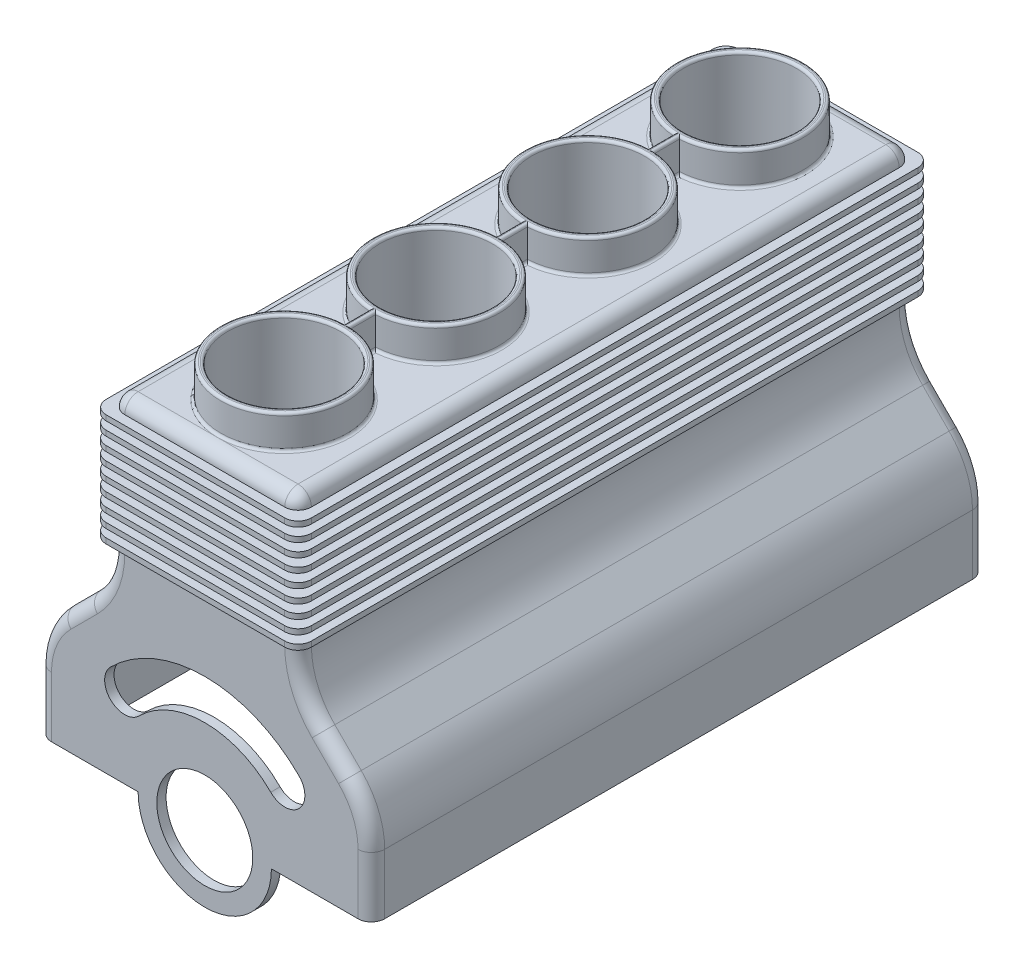
SolidWorks part; units mm, degrees
material "Gray Cast Iron (SN)"
ref_plane "Front Plane" through (0, 0, 0) normal (0, 0, 1) x (1, 0, 0)
ref_plane "Top Plane" through (0, 0, 0) normal (0, 1, 0) x (1, 0, 0)
ref_plane "Right Plane" through (0, 0, 0) normal (1, 0, 0) x (0, 0, -1)
sketch "Sketch1" plane through (0, 0, 0) normal (0, 0, 1) x (1, 0, 0)
  line L0 (0, 0) -> (84554.6019, 0) construction
  line L1 (0, 0) -> (0, 84554.6019) construction
  line L2 (-60, 250) -> (60, 250)
  line L3 (70, 240) -> (70, 149.8528)
  line L4 (125, 45.1472) -> (125, 0)
  line L5 (125, 0) -> (36, 0)
  line L6 (107.4264, 87.5736) -> (87.5736, 107.4264)
  line L7 (-125, 0) -> (-36, 0)
  line L8 (-125, 45.1472) -> (-125, 0)
  line L39 (-70, 240) -> (-70, 149.8528)
  line L40 (-107.4264, 87.5736) -> (-87.5736, 107.4264)
  arc A0 (70, 149.8528) -> (87.5736, 107.4264) centre (130, 149.8528) ccw
  arc A1 (107.4264, 87.5736) -> (125, 45.1472) centre (65, 45.1472) cw
  arc A2 (36, 0) -> (-36, 0) centre (0, 0) ccw
  arc A3 (-107.4264, 87.5736) -> (-125, 45.1472) centre (-65, 45.1472) ccw
  arc A5 (60, 250) -> (70, 240) centre (60, 240) cw
  arc A6 (-70, 240) -> (-60, 250) centre (-60, 240) cw
  arc A7 (-70, 149.8528) -> (-87.5736, 107.4264) centre (-130, 149.8528) cw
  arc A8 (-36, 0) -> (36, 0) centre (0, 0) ccw
  arc A9 (-50, 0) -> (50, 0) centre (0, 0) ccw
  point P16 (120.4328, 68.1082)
  point P25 (70, 125)
  point P29 (0, 250)
  point P32 (70, 250)
  point P35 (-70, 250)
  point P36 (-70, 125)
  dimension "D1" = 36
  dimension "D8" = 10
  dimension "D9" = 60
  dimension "D10" = 50
  dimension "D2" = 140
  dimension "D3" = 250
  dimension "D4" = 250
  dimension "D5" = 60
  dimension "D6" = 135
  dimension "D7" = 125
extrude "Boss-Extrude1" add sketch "Sketch1" along normal mid plane 461 contours A6 A3 L8 L7 A2 L5 L4 A1 L6 A0 | L7 A9 L5 A8 region at (0, 111.7838, 0) region at (-43, -1.118, 0)
sketch "Sketch2" plane through (0, 250, 0) normal (0, 1, 0) x (1, 0, 0)
  line L0 (-50000, 0) -> (50000, 0) construction
  line L1 (-2, 9.5421) -> (-2, -9.5421)
  line L2 (-2, 123.5421) -> (-2, 104.4579)
  line L3 (2, 123.5421) -> (2, 104.4579)
  line L4 (0, 50000) -> (0, -50000) construction
  line L5 (2, 9.5421) -> (2, -9.5421)
  line L6 (-2, -104.4579) -> (-2, -123.5421)
  line L7 (2, -104.4579) -> (2, -123.5421)
  circle A0 centre (0, -171) radius 42.5
  circle A1 centre (0, -57) radius 42.5
  circle A2 centre (0, 57) radius 42.5
  circle A3 centre (0, 171) radius 42.5
  arc A4 (-2, -123.5421) -> (2, -123.5421) centre (0, -171) ccw
  arc A5 (-2, -9.5421) -> (-2, -104.4579) centre (0, -57) ccw
  arc A6 (-2, 104.4579) -> (-2, 9.5421) centre (0, 57) ccw
  arc A7 (2, 123.5421) -> (-2, 123.5421) centre (0, 171) ccw
  arc A8 (2, 9.5421) -> (2, 104.4579) centre (0, 57) ccw
  arc A9 (2, -104.4579) -> (2, -9.5421) centre (0, -57) ccw
  point P21 (0, 0)
  dimension "D1" = 85
  dimension "D4" = 95
  dimension "D3" = 114
  dimension "D6" = 4
  dimension "D2" = 4
  dimension "D5" = 4
ref_plane "Plane1" through (0, 240, 0) normal (0, 1, 0) x (1, 0, 0)
sketch "Sketch3" plane through (0, 240, 0) normal (0, 1, 0) x (1, 0, 0)
  line L0 (70, -230.5) -> (70, 230.5) construction
  line L1 (-67, 237.5) -> (67, 237.5)
  line L2 (-77, 227.5) -> (-77, -227.5)
  line L3 (-67, -237.5) -> (67, -237.5)
  line L4 (77, 227.5) -> (77, -227.5)
  line L5 (-77, 237.5) -> (77, -237.5) construction
  line L6 (-77, -237.5) -> (77, 237.5) construction
  line L10 (60, 230.5) -> (-60, 230.5)
  line L11 (-60, 230.5) -> (-60, -230.5)
  line L12 (-60, -230.5) -> (60, -230.5)
  line L13 (60, -230.5) -> (60, 230.5)
  line L14 (60, 230.5) -> (-60, 230.5)
  line L15 (-60, 230.5) -> (-60, -230.5)
  line L16 (-60, -230.5) -> (60, -230.5)
  line L17 (60, -230.5) -> (60, 230.5)
  arc A0 (-67, 237.5) -> (-77, 227.5) centre (-67, 227.5) ccw
  arc A1 (67, 237.5) -> (77, 227.5) centre (67, 227.5) cw
  arc A2 (67, -237.5) -> (77, -227.5) centre (67, -227.5) ccw
  arc A3 (-77, -227.5) -> (-67, -237.5) centre (-67, -227.5) ccw
  point P0 (0, 0)
  dimension "D4" = 10
  dimension "D2" = 7
  dimension "D3" = 7
  dimension "D1" = 0
extrude "Boss-Extrude2" add sketch "Sketch3" against normal blind 4
pattern_linear "LPattern1" count 9 spacing 10 along (0, -1, 0) of "Boss-Extrude2"
extrude "Cut-Extrude1" cut sketch "Sketch2" against normal blind 114 contours A3 | A2 | A0 | A1 region at (0, 250, 171) region at (0, 250, 57) region at (0, 250, -57) region at (0, 250, -171)
fillet "Fillet2" radius 10 58 edges at (-67.0711, 247.0711, -230.5) (67.0711, 247.0711, -230.5) (-125, 22.5736, -230.5) (-120.4328, 68.1082, -230.5) (-67.0711, 247.0711, 230.5) (67.0711, 247.0711, 230.5) (70, 152.9264, -230.5) (74.5672, 126.8918, -230.5) (97.5, 97.5, -230.5) (125, 22.5736, -230.5) (70, 152.9264, 230.5) (125, 22.5736, 230.5) (120.4328, 68.1082, 230.5) (97.5, 97.5, 230.5) (-70, 152.9264, 230.5) (-74.5672, 126.8918, 230.5) (-97.5, 97.5, 230.5) (-125, 22.5736, 230.5) (0, 250, -230.5) (70, 233, -230.5) (70, 223, -230.5) (70, 213, -230.5) (70, 203, -230.5) (70, 193, -230.5) (70, 183, -230.5) (70, 173, -230.5) (70, 163, -230.5) (-70, 193, -230.5) (-70, 203, -230.5) (-70, 213, -230.5) (-70, 223, -230.5) (-70, 233, -230.5) (-70, 183, -230.5) (-70, 173, -230.5) (-70, 163, -230.5) (-97.5, 97.5, -230.5) (-70, 152.9264, -230.5) (-74.5672, 126.8918, -230.5) (-70, 163, 230.5) (-70, 173, 230.5) (-70, 183, 230.5) (-70, 193, 230.5) (-70, 203, 230.5) (-70, 213, 230.5) (-70, 223, 230.5) (-70, 233, 230.5) (0, 250, 230.5) (70, 233, 230.5) (70, 223, 230.5) (70, 213, 230.5) (70, 203, 230.5) (70, 193, 230.5) (70, 183, 230.5) (70, 173, 230.5) (70, 163, 230.5) (120.4328, 68.1082, -230.5) (74.5672, 126.8918, 230.5) (-120.4328, 68.1082, 230.5)
extrude "Boss-Extrude3" add sketch "Sketch2<3>" along normal blind 25
sketch "Sketch2<3>" plane through (0, 250, 0) normal (0, 1, 0) x (1, 0, 0) same geometry as "Sketch2"
fillet "Fillet3" radius 2 12 edges at (-2, 275, 114) (-47.5, 275, 57) (-2, 275, 0) (-47.5, 275, -57) (-2, 275, -114) (0, 275, -218.5) (2, 275, -114) (2, 275, 0) (47.5, 275, 57) (2, 275, 114) (0, 275, 218.5) (47.5, 275, -57)
fillet "Fillet4" radius 2 16 edges at (-42.5, 275, -57) (-42.5, 275, 57) (-42.5, 275, 171) (0, 250, 218.5) (2, 250, 114) (47.5, 250, 57) (2, 250, 0) (47.5, 250, -57) (2, 250, -114) (0, 250, -218.5) (-2, 250, -114) (-47.5, 250, -57) (-2, 250, 0) (-47.5, 250, 57) (-2, 250, 114) (-42.5, 275, -171)
sketch "Sketch4" plane through (0, 0, 0) normal (0, 0, 1) x (1, 0, 0)
  line L0 (55, 149.8528) -> (55, 151)
  line L1 (55, 151) -> (-55, 151)
  line L2 (-55, 151) -> (-55, 149.8528)
  line L3 (-76.967, 96.8198) -> (-96.8198, 76.967)
  line L4 (-110, 45.1472) -> (-110, 0)
  line L7 (110, 0) -> (110, 45.1472)
  line L8 (96.8198, 76.967) -> (76.967, 96.8198)
  line L10 (-110, 45.1472) -> (-110, 5) construction
  line L11 (110, 5) -> (110, 45.1472) construction
  line L13 (50, 0) -> (115, 0) construction
  line L18 (60, 149.8528) -> (60, 156)
  line L19 (60, 156) -> (-60, 156)
  line L20 (-60, 156) -> (-60, 149.8528)
  line L21 (-80.5025, 100.3553) -> (-100.3553, 80.5025)
  line L22 (-115, 45.1472) -> (-115, 0)
  line L23 (-115, 0) -> (-50, 0)
  line L24 (50, 0) -> (115, 0)
  line L25 (115, 0) -> (115, 45.1472)
  line L26 (100.3553, 80.5025) -> (80.5025, 100.3553)
  line L32 (-115, 0) -> (-50, 0)
  line L33 (50, 0) -> (110, 0)
  line L34 (115, 0) -> (115, 45.1472) construction
  line L36 (-110, 5) -> (-54.7723, 5) construction
  line L37 (54.7723, 5) -> (110, 5) construction
  line L38 (-115, 45.1472) -> (-115, 0) construction
  line L39 (-80.5025, 100.3553) -> (-100.3553, 80.5025) construction
  line L40 (-60, 156) -> (-60, 149.8528) construction
  line L41 (60, 156) -> (-60, 156) construction
  line L42 (60, 149.8528) -> (60, 156) construction
  line L43 (100.3553, 80.5025) -> (80.5025, 100.3553) construction
  arc A0 (-76.967, 96.8198) -> (-55, 149.8528) centre (-130, 149.8528) ccw
  arc A1 (-96.8198, 76.967) -> (-110, 45.1472) centre (-65, 45.1472) ccw
  arc A3 (110, 45.1472) -> (96.8198, 76.967) centre (65, 45.1472) ccw
  arc A4 (55, 149.8528) -> (76.967, 96.8198) centre (130, 149.8528) ccw
  arc A10 (60, 149.8528) -> (80.5025, 100.3553) centre (130, 149.8528) ccw
  arc A11 (-80.5025, 100.3553) -> (-60, 149.8528) centre (-130, 149.8528) ccw
  arc A12 (-100.3553, 80.5025) -> (-115, 45.1472) centre (-65, 45.1472) ccw
  arc A13 (-50, 0) -> (50, 0) centre (0, 0) ccw
  arc A14 (115, 45.1472) -> (100.3553, 80.5025) centre (65, 45.1472) ccw
  arc A20 (54.7723, 5) -> (-54.7723, 5) centre (0, 0) ccw construction
  arc A21 (-100.3553, 80.5025) -> (-115, 45.1472) centre (-65, 45.1472) ccw construction
  arc A22 (-80.5025, 100.3553) -> (-60, 149.8528) centre (-130, 149.8528) ccw construction
  arc A23 (60, 149.8528) -> (80.5025, 100.3553) centre (130, 149.8528) ccw construction
  arc A24 (115, 45.1472) -> (100.3553, 80.5025) centre (65, 45.1472) ccw construction
  arc A25 (50, 0) -> (-50, 0) centre (0, 0) ccw construction
  arc A26 (-50, 0) -> (50, 0) centre (0, 0) ccw
  dimension "D1" = 0
  dimension "D2" = 5
extrude "Cut-Extrude2" cut sketch "Sketch4" against normal blind 217.5 and the other way blind 223.5 contours L33 L7 A3 L8 A4 L0 L1 L2 A0 L3 A1 L4 L32 region at (0, 54.2295, 0)
sketch "Sketch11" plane through (0, 0, -230.5) normal (0, 0, -1) x (-1, 0, 0)
  line L0 (0, 0) -> (0, 113.3679) construction
  arc A0 (-60.1041, 60.1041) -> (60.1041, 60.1041) centre (0, 0) cw construction
  arc A1 (70.7107, 70.7107) -> (-70.7107, 70.7107) centre (0, 0) ccw
  arc A2 (49.4975, 49.4975) -> (-49.4975, 49.4975) centre (0, 0) ccw
  arc A3 (49.4975, 49.4975) -> (70.7107, 70.7107) centre (60.1041, 60.1041) ccw
  arc A4 (-70.7107, 70.7107) -> (-49.4975, 49.4975) centre (-60.1041, 60.1041) ccw
  point P4 (0, 85)
  dimension "D2" = 70
  dimension "D3" = 30
  dimension "D1" = 90
extrude "Cut-Extrude3" cut sketch "Sketch11" against normal through all
